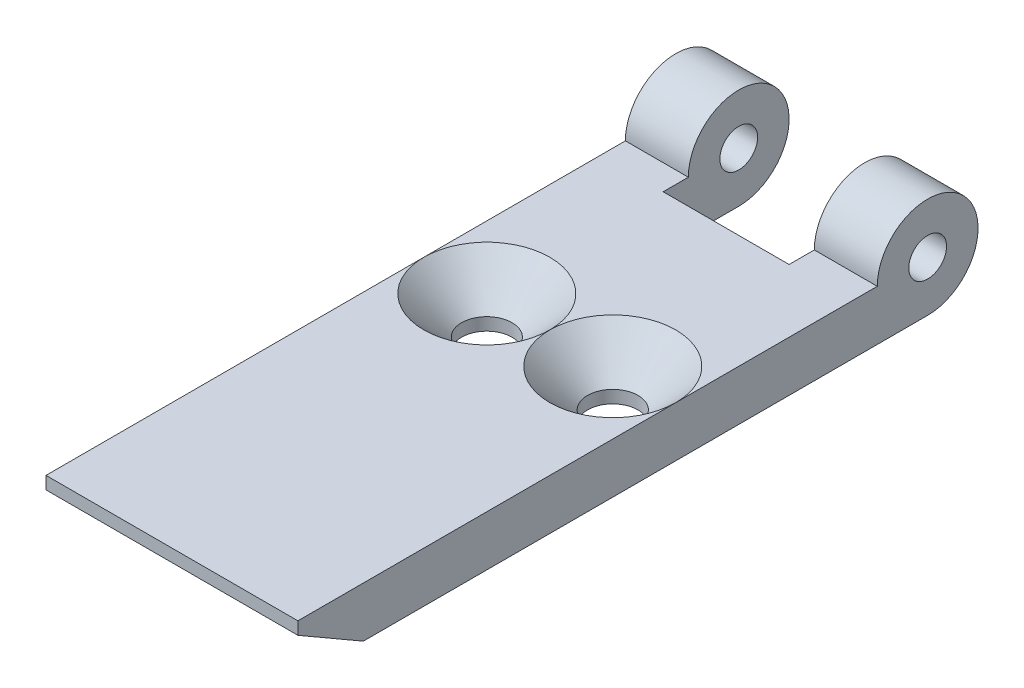
SolidWorks part; units mm, degrees
material "1060 合金"
ref_plane "前视基准面" through (0, 0, 0) normal (0, 0, 1) x (1, 0, 0)
ref_plane "上视基准面" through (0, 0, 0) normal (0, 1, 0) x (1, 0, 0)
ref_plane "右视基准面" through (0, 0, 0) normal (1, 0, 0) x (0, 0, -1)
sketch "草图1" plane through (0, 0, 0) normal (1, 0, 0) x (0, 0, -1)
  line L0 (0, -4) -> (-44.8038, -4)
  line L1 (-44.8038, -4) -> (-50, -1)
  line L2 (-50, -1) -> (-50, 0)
  line L3 (-50, 0) -> (-4, 0)
  arc A0 (0, -4) -> (-4, 0) centre (0, 0) ccw
  circle A1 centre (0, 0) radius 1.5
  dimension "D1" = 4
  dimension "D2" = 3
  dimension "D3" = 50
  dimension "D4" = 1
  dimension "D5" = 30
extrude "凸台-拉伸1" add sketch "草图1" along normal mid plane 20
sketch "草图2" plane through (0, 0, 0) normal (0, 1, 0) x (1, 0, 0)
  line L0 (10, 4) -> (-10, 4) construction
  line L1 (5, 4) -> (-5, 4)
  line L2 (5, 4) -> (5, -6)
  line L3 (5, -6) -> (-5, -6)
  line L4 (-5, 4) -> (-5, -6)
  line L5 (-10, -4) -> (-10, -50) construction
  circle A0 centre (-5, -20) radius 2
  circle A1 centre (5, -20) radius 2
  point P15 (0, 4)
  dimension "D2" = 4
  dimension "D1" = 10
  dimension "D3" = 5
  dimension "D4" = 20
  dimension "D5" = 10
  dimension "D6" = 10
extrude "切除-拉伸1" cut sketch "草图2" against normal through all both and the other way through all
chamfer "倒角1" distance 3 angle 45 2 edges at (5, 0, 18) (-5, 0, 18)
